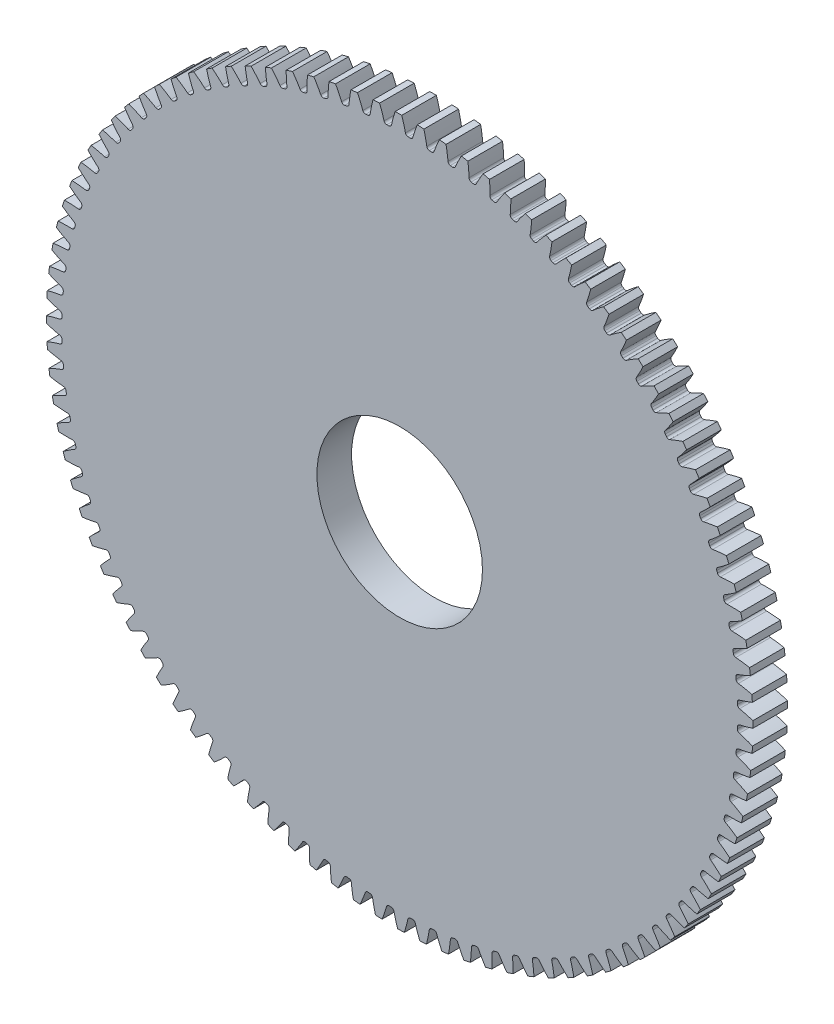
SolidWorks part; units mm, degrees
ref_plane "Front" through (0, 0, 0) normal (0, 0, 1) x (1, 0, 0)
ref_plane "Top" through (0, 0, 0) normal (0, 1, 0) x (1, 0, 0)
ref_plane "Right" through (0, 0, 0) normal (1, 0, 0) x (0, 0, -1)
sketch "Sketch3" plane through (0, 0, 0) normal (0, 0, 1) x (1, 0, 0)
  circle A0 centre (0, 0) radius 129.54
  dimension "od" = 259.08
extrude "gearBody" add sketch "Sketch3" along normal blind 12.7
sketch "Sketch2" plane through (0, 0, 0) normal (0, 0, 1) x (1, 0, 0)
  line L0 (0, 0) -> (113.5954, 47.0527) construction
  line L1 (153.947, -27.2702) -> (0, 0) construction
  line L2 (0, 0) -> (36.3143, 0) construction
  line L3 (126.9908, -1.5267) -> (126.8789, -5.545) construction
  line L5 (126.9349, -3.5358) -> (0, 0) construction
  line L7 (0, 0) -> (122.9548, 0) construction
  arc A0 (122.93, -2.4676) -> (122.8767, -4.3795) centre (0, 0) ccw construction
  arc A1 (129.5378, -0.7514) -> (129.3788, -6.4608) centre (0, 0) ccw construction
  arc A2 (126.9908, -1.5267) -> (126.8789, -5.545) centre (0, 0) ccw construction
  arc A3 (123.8419, -3.8319) -> (123.8632, -3.0681) centre (0, 0) ccw
  arc A4 (153.947, -27.2702) -> (124.5715, -4.8292) centre (110.7999, -53.3034) ccw
  arc A5 (153.947, -27.2702) -> (155.2263, 18.6579) centre (0, 0) ccw
  arc A6 (155.2263, 18.6579) -> (124.6472, -2.1129) centre (113.5954, 47.0527) cw
  arc A7 (123.8632, -3.0681) -> (124.6472, -2.1129) centre (124.8675, -3.093) cw
  arc A8 (124.5715, -4.8292) -> (123.8419, -3.8319) centre (124.846, -3.8629) cw
  point P6 (155.2263, 18.6579)
  point P22 (153.947, -27.2702)
  dimension "baseDia" = 245.9095
  dimension "od" = 259.08
  dimension "pd" = 254
  dimension "rd" = 247.8024
  dimension "rFillet" = 1.0046
  dimension "pointX" = 155.2263
  dimension "pointY" = 18.6579
  dimension "CTT" = 4.0183
  dimension "flankCenterAngle" = 22.5
extrude "toothCut" cut sketch "Sketch2" along normal through all
pattern_circular "CirPattern1" count 100 over 360 about axis through (0, 0, 12.7) along (0, 0, -1) of "toothCut"
ref_axis "toothSpace" through (0, 0, 0) along (0.9996, -0.0278, 0)
ref_axis "Axis2" through (129.3126, -7.6726, 0) along (-0.9982, 0.0592, 0)
sketch "hub1Dia" plane through (0, 0, 0) normal (0, 0, -1) x (-1, 0, 0)
  circle A0 centre (0, 0) radius 12.7
  dimension "hub1Dia" = 25.4
sketch "hub2Dia" plane through (0, 0, 12.7) normal (0, 0, 1) x (1, 0, 0)
  circle A0 centre (0, 0) radius 12.7
  dimension "hub2dia" = 25.4
sketch "boreDia" plane through (0, 0, 0) normal (0, 0, 1) x (1, 0, 0)
  circle A0 centre (0, 0) radius 30.353
  dimension "boreDia" = 60.706
extrude "bore" cut sketch "boreDia" against normal mid plane 25400
sketch "kwy1sketch" plane through (0, 0, 0) normal (0, 0, 1) x (1, 0, 0)
  line L0 (-5.3237, 0.26) -> (0, 0) construction
  line L1 (56.3061, 9.9656) -> (55.0672, -15.4041)
  line L2 (55.0672, -15.4041) -> (23.355, -13.8556)
  line L3 (56.3061, 9.9656) -> (24.5939, 11.5142)
  line L4 (23.355, -13.8556) -> (0, 0)
  line L5 (0, 0) -> (24.5939, 11.5142)
  line L6 (0, 0) -> (123.8532, -3.45) construction
  line L7 (55.6866, -2.7192) -> (0, 0) construction
  arc A7 (123.8419, -3.8319) -> (123.8632, -3.0681) centre (0, 0) ccw construction
  point P9 (55.6866, -2.7192)
  point P13 (-0.888, 0.0434)
  dimension "kwy1width" = 25.4
  dimension "kwy1depth" = 55.753
  dimension "kwy1angle" = 1.2
  dimension "kwy1Depth2" = 31.75
sketch "kwy2sketch" plane through (0, 0, 0) normal (0, 0, 1) x (1, 0, 0)
  line L0 (123.8532, -3.45) -> (0, 0) construction
  line L1 (0, 0) -> (-2.7284, -2.4743) construction
  line L2 (32.7676, 46.8612) -> (49.8308, 28.0461)
  line L3 (49.8308, 28.0461) -> (26.3119, 6.7171)
  line L4 (32.7676, 46.8612) -> (9.2487, 25.5322)
  line L5 (26.3119, 6.7171) -> (0, 0)
  line L6 (0, 0) -> (9.2487, 25.5322)
  arc A2 (123.8419, -3.8319) -> (123.8632, -3.0681) centre (0, 0) ccw construction
  point P10 (41.2992, 37.4536)
  dimension "kwy2angle" = 43.8
  dimension "kwy2Width" = 25.4
  dimension "kwy2depth" = 55.753
  dimension "kwy2Depth2" = 31.75
sketch "kwy3sketch" plane through (0, 0, 0) normal (0, 0, 1) x (1, 0, 0)
  line L0 (123.8532, -3.45) -> (0, 0) construction
  line L1 (0, 0) -> (-0.13, -2.6615) construction
  line L2 (-9.9656, 56.3061) -> (15.4041, 55.0672)
  line L3 (15.4041, 55.0672) -> (13.8556, 23.355)
  line L4 (-9.9656, 56.3061) -> (-11.5142, 24.5939)
  line L5 (13.8556, 23.355) -> (0, 0)
  line L6 (-11.5142, 24.5939) -> (0, 0)
  point P10 (2.7192, 55.6866)
  dimension "kwy3angle" = 88.8
  dimension "kwy3depth" = 55.753
  dimension "kwy3width" = 25.4
  dimension "kwy3Depth2" = 31.75
sketch "kwy4sketch" plane through (0, 0, 0) normal (0, 0, 1) x (1, 0, 0)
  line L0 (123.8532, -3.45) -> (0, 0) construction
  line L1 (0, 0) -> (1.3996, -1.5434) construction
  line L2 (-28.0461, 49.8308) -> (-46.8612, 32.7676)
  line L3 (-46.8612, 32.7676) -> (-25.5322, 9.2487)
  line L4 (-25.5322, 9.2487) -> (0, 0)
  line L5 (-6.7171, 26.3119) -> (0, 0)
  line L6 (-28.0461, 49.8308) -> (-6.7171, 26.3119)
  point P15 (-37.4536, 41.2992)
  dimension "kwy4angle" = 133.8
  dimension "kwy4depth" = 55.753
  dimension "kwy4width" = 25.4
  dimension "kwy4Depth2" = 31.75
sketch "kwy5sketch" plane through (0, 0, 0) normal (0, 0, 1) x (1, 0, 0)
  line L0 (123.8532, -3.45) -> (0, 0) construction
  line L1 (0, 0) -> (1.7872, -0.0873) construction
  line L2 (-55.0672, 15.4041) -> (-56.3061, -9.9656)
  line L3 (-56.3061, -9.9656) -> (-24.5939, -11.5142)
  line L4 (-55.0672, 15.4041) -> (-23.355, 13.8556)
  line L5 (-24.5939, -11.5142) -> (0, 0)
  line L6 (-23.355, 13.8556) -> (0, 0)
  point P10 (-55.6866, 2.7192)
  dimension "kwy5width" = 25.4
  dimension "kwy5depth" = 55.753
  dimension "kwy5angle" = 178.8
  dimension "kwy5Depth2" = 31.75
sketch "kwy6sketch" plane through (0, 0, 0) normal (0, 0, 1) x (1, 0, 0)
  line L0 (123.8532, -3.45) -> (0, 0) construction
  line L1 (0, 0) -> (1.3244, 1.2011) construction
  line L2 (-49.8308, -28.0461) -> (-32.7676, -46.8612)
  line L3 (-32.7676, -46.8612) -> (-9.2487, -25.5322)
  line L4 (-49.8308, -28.0461) -> (-26.3119, -6.7171)
  line L5 (-9.2487, -25.5322) -> (0, 0)
  line L6 (-26.3119, -6.7171) -> (0, 0)
  point P10 (-41.2992, -37.4536)
  dimension "kwy6angle" = 223.8
  dimension "kwy6width" = 25.4
  dimension "kwy6depth" = 55.753
  dimension "kwy6Depth2" = 31.75
sketch "kwy7sketch" plane through (0, 0, 0) normal (0, 0, 1) x (1, 0, 0)
  line L0 (123.8532, -3.45) -> (0, 0) construction
  line L1 (0, 0) -> (0.0977, 2.0007) construction
  line L2 (-15.4041, -55.0672) -> (9.9656, -56.3061)
  line L3 (-15.4041, -55.0672) -> (-13.8556, -23.355)
  line L4 (9.9656, -56.3061) -> (11.5142, -24.5939)
  line L5 (-13.8556, -23.355) -> (0, 0)
  line L6 (11.5142, -24.5939) -> (0, 0)
  point P10 (-2.7192, -55.6866)
  dimension "kwy7angle" = 88.8
  dimension "kwy7width" = 25.4
  dimension "kwy7depth" = 55.753
  dimension "kwy7angle1" = 268.8
  dimension "kwy7Depth2" = 31.75
sketch "kwy8sketch" plane through (0, 0, 0) normal (0, 0, 1) x (1, 0, 0)
  line L0 (123.8532, -3.45) -> (0, 0) construction
  line L1 (0, 0) -> (-1.1955, 1.3183) construction
  line L2 (28.0461, -49.8308) -> (46.8612, -32.7676)
  line L3 (46.8612, -32.7676) -> (25.5322, -9.2487)
  line L4 (28.0461, -49.8308) -> (6.7171, -26.3119)
  line L5 (25.5322, -9.2487) -> (0, 0)
  line L6 (6.7171, -26.3119) -> (0, 0)
  point P10 (37.4536, -41.2992)
  dimension "kwy8angle" = 313.8
  dimension "kwy8width" = 25.4
  dimension "kwy8depth" = 55.753
  dimension "kwy8Depth2" = 31.75
sketch "centerLine" plane through (0, 0, 0) normal (0, 1, 0) x (1, 0, 0)
  line L0 (0, 36.4807) -> (0, -59.6309) construction
ref_plane "CB1plane" through (0, 0, 0) normal (0, 0, -1) x (-1, 0, 0)
sketch "CB1diameter" plane through (0, 0, 0) normal (0, 0, -1) x (-1, 0, 0)
  circle A0 centre (0, 0) radius 12.7
  dimension "CB1diameter" = 25.4
ref_plane "CB2plane" through (0, 0, 12.7) normal (0, 0, 1) x (1, 0, 0)
sketch "CB2diameter" plane through (0, 0, 12.7) normal (0, 0, 1) x (1, 0, 0)
  circle A0 centre (0, 0) radius 12.7
  dimension "CB2diameter" = 25.4
ref_axis "Axis1" through (0, 0, 50) along (0, 0, -1)
sketch3d "3DSketch1" plane through (0, 0, 0) normal (0, 0, 1) x (1, 0, 0)
